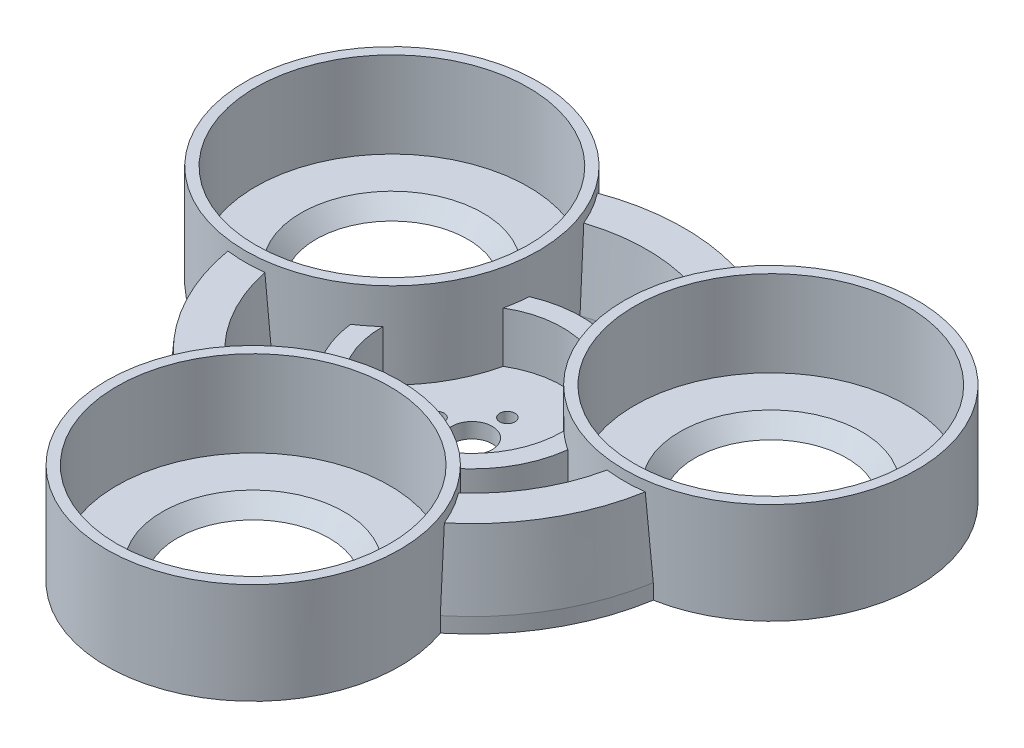
SolidWorks part; units mm, degrees
ref_plane "前视基准面" through (0, 0, 0) normal (0, 0, 1) x (1, 0, 0)
ref_plane "上视基准面" through (0, 0, 0) normal (0, 1, 0) x (1, 0, 0)
ref_plane "右视基准面" through (0, 0, 0) normal (1, 0, 0) x (0, 0, -1)
other "Configuration Table"
sketch "草图1" plane through (0, 0, 0) normal (0, 1, 0) x (1, 0, 0)
  line L0 (0, 0) -> (75, 0) construction
  line L1 (0, 0) -> (37.5, -64.9519) construction
  line L2 (75, 0) -> (37.5, -64.9519) construction
  circle A0 centre (0, 0) radius 25 construction
  circle A1 centre (75, 0) radius 25 construction
  circle A2 centre (37.5, -64.9519) radius 25 construction
  circle A4 centre (37.5, -21.6506) radius 43.3013 construction
  circle A5 centre (75, 0) radius 29
  circle A6 centre (37.5, -64.9519) radius 29
  circle A7 centre (0, 0) radius 29
  circle A8 centre (37.5, -21.6506) radius 33.3013 construction
  arc A9 (27.2132, 10.022) -> (47.7868, 10.022) centre (37.5, -21.6506) cw
  arc A10 (22.0729, 18.8093) -> (52.9271, 18.8093) centre (37.5, -21.6506) cw
  arc A11 (-5.0591, -28.5553) -> (10.2408, -55.0555) centre (37.5, -21.6506) ccw
  arc A12 (4.9273, -28.5783) -> (15.2141, -46.3956) centre (37.5, -21.6506) ccw
  arc A13 (80.2529, -28.5203) -> (64.8257, -55.2409) centre (37.5, -21.6506) cw
  arc A14 (70.0727, -28.5783) -> (59.7859, -46.3956) centre (37.5, -21.6506) cw
  circle A15 centre (37.5, -21.6506) radius 21.6506
  dimension "D1" = 50
  dimension "D3" = 50
  dimension "D6" = 50
  dimension "D7" = 4
  dimension "D8" = 4
  dimension "D9" = 4
  dimension "D10" = 10
  dimension "D2" = 75
  dimension "D4" = 60
  dimension "D5" = 75
extrude "凸台-拉伸1" add sketch "草图1" along normal blind 3 contours A10 A7 A9 A5 | A7 | A5 | A12 A7 A11 A6 | A6 | A5 A14 A6 A13 | A15 region at (76.1314, 0, -0.6532) region at (37.5, 0, -16.2701) region at (70.3403, 0, 40.611) region at (-1.1314, 0, -0.6532) region at (37.5, 0, 66.2583) region at (4.7473, 0, 40.5604)
sketch "草图2" plane through (0, 3, 0) normal (0, 1, 0) x (1, 0, 0)
  circle A0 centre (0, 0) radius 27
  circle A1 centre (0, 0) radius 29
  circle A2 centre (37.5, -64.9519) radius 27
  circle A3 centre (75, 0) radius 27
  circle A4 centre (37.5, -64.9519) radius 29
  circle A5 centre (75, 0) radius 29
  dimension "D1" = 54
  dimension "D2" = 54
  dimension "D3" = 54
extrude "凸台-拉伸2" add sketch "草图2" along normal blind 25
sketch "草图3" plane through (0, 0, 0) normal (0, -1, 0) x (1, 0, 0)
  line L0 (37.5, 21.6506) -> (0, 0) construction
  line L1 (37.5, 64.9519) -> (37.5, 21.6506) construction
  line L2 (37.5, 21.6506) -> (75, 0) construction
  circle A0 centre (37.5, 64.9519) radius 15
  circle A1 centre (75, 0) radius 15
  circle A2 centre (0, 0) radius 15
  dimension "D1" = 30
  dimension "D2" = 30
  dimension "D3" = 30
extrude "切除-拉伸1" cut sketch "草图3" against normal up to next
sketch "草图5" plane through (0, 3, 0) normal (0, 1, 0) x (1, 0, 0)
  arc A1 (19.6048, -21.3694) -> (28.7959, -37.2889) centre (37.5, -21.6506) ccw
  arc A2 (46.6911, -6.2935) -> (28.3089, -6.2935) centre (37.5, -21.6506) ccw
  arc A3 (46.2041, -37.2889) -> (55.3952, -21.3694) centre (37.5, -21.6506) ccw
  arc A4 (47.7868, 10.022) -> (27.2132, 10.022) centre (37.5, -21.6506) ccw
  arc A5 (52.9271, 18.8093) -> (47.7868, 10.022) centre (75, 0) ccw
  arc A6 (52.9271, 18.8093) -> (22.0729, 18.8093) centre (37.5, -21.6506) ccw
  arc A7 (27.2132, 10.022) -> (22.0729, 18.8093) centre (0, 0) ccw
  arc A8 (47.7868, 10.022) -> (27.2132, 10.022) centre (37.5, -21.6506) ccw
  arc A9 (52.9271, 18.8093) -> (47.7868, 10.022) centre (75, 0) ccw
  arc A10 (52.9271, 18.8093) -> (22.0729, 18.8093) centre (37.5, -21.6506) ccw
  arc A11 (27.2132, 10.022) -> (22.0729, 18.8093) centre (0, 0) ccw
  arc A12 (64.8257, -55.2409) -> (80.2529, -28.5203) centre (37.5, -21.6506) ccw
  arc A13 (70.0727, -28.5783) -> (80.2529, -28.5203) centre (75, 0) ccw
  arc A14 (59.7859, -46.3956) -> (70.0727, -28.5783) centre (37.5, -21.6506) ccw
  arc A15 (64.8257, -55.2409) -> (59.7859, -46.3956) centre (37.5, -64.9519) ccw
  arc A16 (64.8257, -55.2409) -> (80.2529, -28.5203) centre (37.5, -21.6506) ccw
  arc A17 (70.0727, -28.5783) -> (80.2529, -28.5203) centre (75, 0) ccw
  arc A18 (59.7859, -46.3956) -> (70.0727, -28.5783) centre (37.5, -21.6506) ccw
  arc A19 (64.8257, -55.2409) -> (59.7859, -46.3956) centre (37.5, -64.9519) ccw
  arc A20 (-5.0591, -28.5553) -> (10.2408, -55.0555) centre (37.5, -21.6506) ccw
  arc A21 (15.2141, -46.3956) -> (10.2408, -55.0555) centre (37.5, -64.9519) ccw
  arc A22 (4.9273, -28.5783) -> (15.2141, -46.3956) centre (37.5, -21.6506) ccw
  arc A23 (-5.0591, -28.5553) -> (4.9273, -28.5783) centre (0, 0) ccw
  arc A24 (-5.0591, -28.5553) -> (10.2408, -55.0555) centre (37.5, -21.6506) ccw
  arc A25 (15.2141, -46.3956) -> (10.2408, -55.0555) centre (37.5, -64.9519) ccw
  arc A26 (4.9273, -28.5783) -> (15.2141, -46.3956) centre (37.5, -21.6506) ccw
  arc A27 (-5.0591, -28.5553) -> (4.9273, -28.5783) centre (0, 0) ccw
  arc A28 (28.3089, -6.2935) -> (28.9465, -1.7613) centre (0, 0) ccw
  arc A29 (55.3952, -21.3694) -> (59.0015, -24.1877) centre (75, 0) ccw
  arc A30 (50.4479, -39.0029) -> (59.0015, -24.1877) centre (37.5, -21.6506) ccw
  arc A31 (46.0535, -1.7613) -> (59.0015, -24.1877) centre (75, 0) ccw
  arc A32 (46.0535, -1.7613) -> (28.9465, -1.7613) centre (37.5, -21.6506) ccw
  arc A33 (15.9985, -24.1877) -> (28.9465, -1.7613) centre (0, 0) ccw
  arc A34 (15.9985, -24.1877) -> (24.5521, -39.0029) centre (37.5, -21.6506) ccw
  arc A35 (50.4479, -39.0029) -> (24.5521, -39.0029) centre (37.5, -64.9519) ccw
  arc A36 (50.4479, -39.0029) -> (59.0015, -24.1877) centre (37.5, -21.6506) ccw
  arc A37 (46.0535, -1.7613) -> (46.6911, -6.2935) centre (75, 0) ccw
  arc A38 (46.0535, -1.7613) -> (28.9465, -1.7613) centre (37.5, -21.6506) ccw
  arc A39 (15.9985, -24.1877) -> (19.6048, -21.3694) centre (0, 0) ccw
  arc A40 (15.9985, -24.1877) -> (24.5521, -39.0029) centre (37.5, -21.6506) ccw
  arc A41 (50.4479, -39.0029) -> (46.2041, -37.2889) centre (37.5, -64.9519) ccw
  arc A42 (28.7959, -37.2889) -> (24.5521, -39.0029) centre (37.5, -64.9519) ccw
  dimension "D1" = 0
  dimension "D2" = 0
  dimension "D3" = 0
  dimension "D4" = 0
extrude "凸台-拉伸4" add sketch "草图5" along normal blind 15
sketch "草图6" plane through (0, 18, 0) normal (0, 1, 0) x (1, 0, 0)
  arc A4 (15.9985, -24.1877) -> (19.6048, -21.3694) centre (0, 0) ccw
  arc A5 (15.9985, -24.1877) -> (24.5521, -39.0029) centre (37.5, -21.6506) ccw
  arc A6 (28.7959, -37.2889) -> (24.5521, -39.0029) centre (37.5, -64.9519) ccw
  arc A7 (19.6048, -21.3694) -> (28.7959, -37.2889) centre (37.5, -21.6506) ccw
  arc A8 (15.9985, -24.1877) -> (19.6048, -21.3694) centre (0, 0) ccw
  arc A9 (15.9985, -24.1877) -> (24.5521, -39.0029) centre (37.5, -21.6506) ccw
  arc A10 (28.7959, -37.2889) -> (24.5521, -39.0029) centre (37.5, -64.9519) ccw
  arc A11 (19.6048, -21.3694) -> (28.7959, -37.2889) centre (37.5, -21.6506) ccw
  arc A12 (28.3089, -6.2935) -> (28.9465, -1.7613) centre (0, 0) ccw
  arc A13 (46.6911, -6.2935) -> (28.3089, -6.2935) centre (37.5, -21.6506) ccw
  arc A14 (46.0535, -1.7613) -> (46.6911, -6.2935) centre (75, 0) ccw
  arc A15 (46.0535, -1.7613) -> (28.9465, -1.7613) centre (37.5, -21.6506) ccw
  arc A16 (28.3089, -6.2935) -> (28.9465, -1.7613) centre (0, 0) ccw
  arc A17 (46.6911, -6.2935) -> (28.3089, -6.2935) centre (37.5, -21.6506) ccw
  arc A18 (46.0535, -1.7613) -> (46.6911, -6.2935) centre (75, 0) ccw
  arc A19 (46.0535, -1.7613) -> (28.9465, -1.7613) centre (37.5, -21.6506) ccw
  arc A20 (55.3952, -21.3694) -> (59.0015, -24.1877) centre (75, 0) ccw
  arc A21 (46.2041, -37.2889) -> (55.3952, -21.3694) centre (37.5, -21.6506) ccw
  arc A22 (50.4479, -39.0029) -> (46.2041, -37.2889) centre (37.5, -64.9519) ccw
  arc A23 (50.4479, -39.0029) -> (59.0015, -24.1877) centre (37.5, -21.6506) ccw
  arc A24 (55.3952, -21.3694) -> (59.0015, -24.1877) centre (75, 0) ccw
  arc A25 (46.2041, -37.2889) -> (55.3952, -21.3694) centre (37.5, -21.6506) ccw
  arc A26 (50.4479, -39.0029) -> (46.2041, -37.2889) centre (37.5, -64.9519) ccw
  arc A27 (50.4479, -39.0029) -> (59.0015, -24.1877) centre (37.5, -21.6506) ccw
  dimension "D1" = 0
  dimension "D2" = 0
  dimension "D3" = 0
extrude "切除-拉伸2" cut sketch "草图6" against normal blind 5
chamfer "倒角1" distance 3 angle 45 3 edges at (37.5, 3, 79.9519) (75, 3, 15) (0, 3, 15)
chamfer "倒角2" distance 15 angle 5 6 edges at (66.3397, 18, 38.3013) (75, 18, 43.3013) (37.5, 18, -21.6506) (37.5, 18, -11.6506) (8.6603, 18, 38.3013) (0.1609, 18, 43.2084) first distance on face at (65.6345, 9, 37.8941) first distance on face at (73.7697, 9, 42.5909) first distance on face at (37.5, 9, -20.23) first distance on face at (37.5, 9, -10.8363) first distance on face at (9.3655, 9, 37.8941) first distance on face at (1.3759, 9, 42.5069)
sketch "草图8" plane through (0, 28, 0) normal (0, 1, 0) x (1, 0, 0)
  circle A0 centre (0, 0) radius 29 construction
  circle A1 centre (0, 0) radius 29
  circle A3 centre (75, 0) radius 29
  circle A4 centre (75, 0) radius 29
  circle A5 centre (37.5, -64.9519) radius 29
  circle A6 centre (37.5, -64.9519) radius 29
  dimension "D1" = 0
  dimension "D2" = 0
extrude "切除-拉伸3" cut sketch "草图8" against normal blind 8
sketch "草图10" plane through (0, 3, 0) normal (0, 1, 0) x (1, 0, 0)
  line L0 (37.5, -21.6506) -> (44.5, -21.6506) construction
  line L1 (37.5, -21.6506) -> (37.5, -14.6506) construction
  line L2 (37.5, -21.6506) -> (30.5, -21.6506) construction
  line L3 (37.5, -21.6506) -> (37.5, -28.6506) construction
  line L4 (37.5, -64.9519) -> (37.5, -21.6506) construction
  circle A0 centre (44.5, -21.6506) radius 1.5
  circle A1 centre (37.5, -14.6506) radius 1.5
  circle A2 centre (30.5, -21.6506) radius 1.5
  circle A3 centre (37.5, -28.6506) radius 1.5
  circle A4 centre (37.5, -21.6506) radius 4
  dimension "D5" = 3
  dimension "D6" = 3
  dimension "D7" = 3
  dimension "D8" = 3
  dimension "D9" = 8
  dimension "D1" = 7
  dimension "D2" = 7
  dimension "D3" = 7
  dimension "D4" = 7
extrude "切除-拉伸4" cut sketch "草图10" against normal up to next
